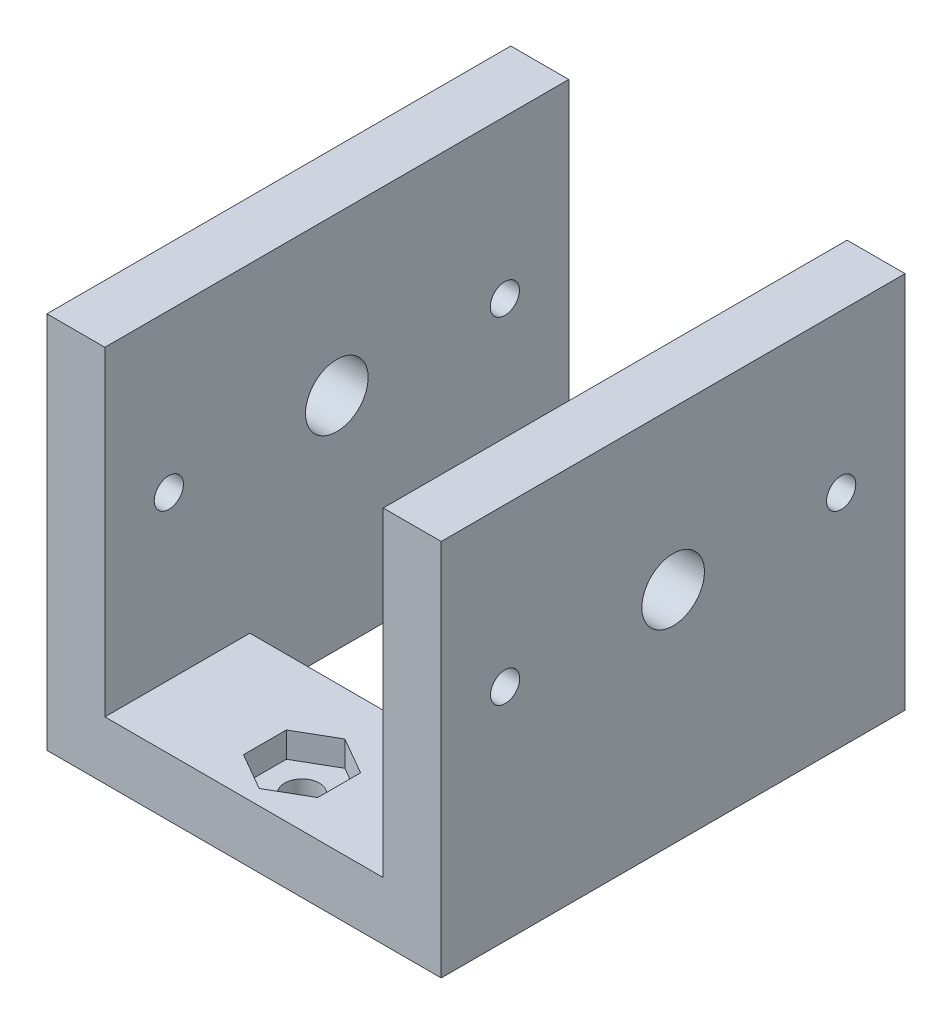
SolidWorks part; units mm, degrees
ref_plane "Front Plane" through (0, 0, 0) normal (0, 0, 1) x (1, 0, 0)
ref_plane "Top Plane" through (0, 0, 0) normal (0, 1, 0) x (1, 0, 0)
ref_plane "Right Plane" through (0, 0, 0) normal (1, 0, 0) x (0, 0, -1)
sketch "Sketch1" plane through (0, 0, 0) normal (0, 0, 1) x (1, 0, 0)
  line L0 (-26.9408, -26.9408) -> (0, 0) construction
  line L1 (0, 0) -> (26.9408, -26.9408) construction
  line L2 (-45.4545, 0) -> (50.5549, 0) construction
  line L7 (-26.9408, -17.4158) -> (-26.9408, 39.7342)
  line L9 (26.9408, 39.7342) -> (26.9408, -17.4158)
  line L11 (15, -48.5349) -> (-15, -48.5349) construction
  line L12 (-26.9408, -36.4658) -> (26.9408, -36.4658)
  line L13 (-26.9408, 39.7342) -> (26.9408, 39.7342)
  line L14 (-26.9408, 26.9408) -> (0, 0) construction
  line L15 (26.9408, 26.9408) -> (0, 0) construction
  circle A0 centre (0, 0) radius 38.1 construction
  circle A1 centre (-26.9408, -26.9408) radius 4.445
  circle A2 centre (26.9408, -26.9408) radius 4.445
  arc A3 (-26.9408, -17.4158) -> (-26.9408, -36.4658) centre (-26.9408, -26.9408) ccw
  arc A4 (26.9408, -36.4658) -> (26.9408, -17.4158) centre (26.9408, -26.9408) ccw
  circle A5 centre (0, 0) radius 50.8 construction
  circle A6 centre (-26.9408, 26.9408) radius 9.525 construction
  circle A7 centre (26.9408, 26.9408) radius 9.525 construction
  dimension "D1" = 76.2
  dimension "D4" = 8.89
  dimension "D5" = 8.89
  dimension "D6" = 19.05
  dimension "D7" = 19.05
  dimension "D8" = 57.15
  dimension "D9" = 101.6
  dimension "D11" = 19.05
  dimension "D13" = 19.05
  dimension "D2" = 45
  dimension "D3" = 45
  dimension "D10" = 30
  dimension "D12" = 45
  dimension "D14" = 45
extrude "Boss-Extrude1" add sketch "Sketch1" along normal blind 12.7 and the other way blind 12.7
sketch "Sketch9" plane through (0, 0, 12.7) normal (0, 0, 1) x (1, 0, 0)
  line L0 (-26.9408, 39.7342) -> (26.9408, 39.7342) construction
  line L1 (-15.24, 39.7342) -> (15.24, 39.7342)
  line L2 (-15.24, 39.7342) -> (-15.24, 4.6822)
  line L3 (-15.24, 4.6822) -> (15.24, 4.6822)
  line L4 (15.24, 39.7342) -> (15.24, 4.6822)
  line L5 (-15.24, 39.7342) -> (15.24, 4.6822) construction
  line L6 (-15.24, 4.6822) -> (15.24, 39.7342) construction
  point P0 (0, 22.2082)
  dimension "D1" = 30.48
  dimension "D2" = 35.052
extrude "Cut-Extrude6" cut sketch "Sketch9" against normal through all
sketch "Sketch10" plane through (0, 0, 12.7) normal (0, 0, 1) x (1, 0, 0)
  line L0 (-26.9408, 39.7342) -> (-26.9408, -1.6678)
  line L2 (-26.9408, -1.6678) -> (26.9408, -1.6678)
  line L3 (26.9408, 39.7342) -> (26.9408, -17.4158) construction
  line L5 (26.9408, -1.6678) -> (26.9408, 39.7342)
  line L6 (26.9408, 39.7342) -> (15.24, 39.7342)
  line L7 (15.24, 39.7342) -> (15.24, 4.6822)
  line L8 (15.24, 4.6822) -> (-15.24, 4.6822)
  line L9 (-15.24, 4.6822) -> (-15.24, 39.7342)
  line L10 (-15.24, 39.7342) -> (-26.9408, 39.7342)
  dimension "D1" = 6.35
extrude "Boss-Extrude3" add sketch "Sketch10" along normal blind 12.7
mirror "Mirror4" about plane through (0, 0, 0) normal (0, 0, 1) of "Boss-Extrude3"
sketch "Sketch11" plane through (0, 0, 25.4) normal (0, 0, 1) x (1, 0, 0)
  line L1 (-26.9408, 39.7342) -> (-21.59, 39.7342)
  line L2 (-26.9408, 39.7342) -> (-26.9408, -17.4158)
  line L3 (-26.9408, -17.4158) -> (-21.59, -17.4158)
  line L4 (-21.59, 39.7342) -> (-21.59, -17.4158)
  line L5 (-15.24, 4.6822) -> (-15.24, 39.7342) construction
  dimension "D1" = 6.35
extrude "Cut-Extrude7" cut sketch "Sketch11" against normal through all
mirror "Mirror5" about plane through (0, 0, 0) normal (1, 0, 0) of "Cut-Extrude7"
sketch "Sketch12" plane through (0, -36.4658, 0) normal (0, -1, 0) x (1, 0, 0)
  line L0 (15.24, -25.4) -> (15.24, 25.4) construction
  line L1 (-15.24, 9.525) -> (15.24, 9.525)
  line L2 (-15.24, 9.525) -> (-15.24, -9.525)
  line L3 (-15.24, -9.525) -> (15.24, -9.525)
  line L4 (15.24, 9.525) -> (15.24, -9.525)
  line L5 (-15.24, 9.525) -> (15.24, -9.525) construction
  line L6 (-15.24, -9.525) -> (15.24, 9.525) construction
  point P0 (0, 0)
  point P2 (15.24, 9.525)
  dimension "D1" = 19.05
extrude "Cut-Extrude8" cut sketch "Sketch12" against normal through all
sketch "Sketch14" plane through (-21.59, 0, 0) normal (-1, 0, 0) x (0, 0, 1)
  line L0 (-25.4, 4.6822) -> (-9.525, 4.6822) construction
  circle A0 centre (-18.4, 22.4622) radius 1.6
  dimension "D1" = 3.2
  dimension "D2" = 17.78
  dimension "D3" = 18.4
extrude "Cut-Extrude9" cut sketch "Sketch14" against normal through all
mirror "Mirror6" about plane through (0, 0, 0) normal (0, 0, 1) of "Cut-Extrude9"
sketch "Sketch15" plane through (21.59, 0, 0) normal (1, 0, 0) x (0, 0, -1)
  line L0 (0, -17.4158) -> (0, 39.7342) construction
  line L1 (-18.4, 22.4622) -> (18.4, 22.4622) construction
  line L2 (0, 38.1) -> (0, -38.1) construction
  circle A0 centre (0, 22.4622) radius 3.429
  dimension "D1" = 6.858
extrude "Cut-Extrude10" cut sketch "Sketch15" against normal through all
sketch "Sketch18" plane through (0, 4.6822, 0) normal (0, 1, 0) x (1, 0, 0)
  line L0 (-26.9408, 0) -> (26.9408, 0) construction
  line L1 (4.064, 21.3964) -> (0, 23.7427)
  line L2 (0, 23.7427) -> (-4.064, 21.3964)
  line L3 (-4.064, 21.3964) -> (-4.064, 16.7036)
  line L4 (-4.064, 16.7036) -> (0, 14.3573)
  line L5 (0, 14.3573) -> (4.064, 16.7036)
  line L6 (4.064, 16.7036) -> (4.064, 21.3964)
  circle A0 centre (0, 19.05) radius 4.064 construction
  point P1 (-10.414, 17.3524)
  point P9 (-10.414, 16.6574)
  point P10 (-10.414, 0)
  point P11 (-0.0041, 16.8504)
  point P12 (0, 21.3773)
  dimension "D1" = 8.128
  dimension "D2" = 19.05
extrude "Cut-Extrude11" cut sketch "Sketch18" against normal blind 2.7781
mirror "Mirror7" about plane through (0, 0, 0) normal (0, 0, 1) of "Cut-Extrude11"
hole_wizard "#6 Clearance Hole1" positions "Sketch20" profile "Sketch22" hole size "#6" standard "ANSI Inch" end condition through all
sketch "Sketch20" plane through (0, 1.9041, 0) normal (0, 1, 0) x (1, 0, 0)
  line L1 (0, 23.7427) -> (0, 14.3573) construction
  point P0 (0, 19.05)
  point P10 (-9.6167, 0)
  point P11 (0, 19.05)
sketch "Sketch22" plane through (0, 1.9041, -19.05) normal (1, 0, 0) x (0, 0, 1)
  line L0 (0, 0) -> (0, 38.3699)
  line L1 (0, 38.3699) -> (1.8986, 38.3699)
  line L2 (1.8986, 38.3699) -> (1.8986, 0)
  line L5 (1.8986, 0) -> (0, 0)
  line L11 (0, -6.35) -> (0, 107.95) construction
  dimension "Thru Hole Dia." = 3.7973
  dimension "Thru Hole Depth" = 38.3699
mirror "Mirror8" about plane through (0, 0, 0) normal (0, 0, 1) of "#6 Clearance Hole1"
sketch "Sketch24" plane through (0, 0, -25.4) normal (0, 0, -1) x (-1, 0, 0)
  line L1 (-21.59, -1.6678) -> (21.59, -1.6678)
  line L2 (-21.59, -1.6678) -> (-21.59, 39.7342)
  line L3 (-21.59, 39.7342) -> (21.59, 39.7342)
  line L4 (21.59, -1.6678) -> (21.59, 39.7342)
sketch "Sketch25" plane through (0, 0, -12.7) normal (0, 0, -1) x (-1, 0, 0)
  line L0 (-21.59, -1.6678) -> (21.59, -1.6678) construction
  line L1 (-44.148, -1.6678) -> (45.6656, -1.6678)
  line L2 (-44.148, -1.6678) -> (-44.148, -41.125)
  line L3 (-44.148, -41.125) -> (45.6656, -41.125)
  line L4 (45.6656, -1.6678) -> (45.6656, -41.125)
extrude "Cut-Extrude14" cut sketch "Sketch25" against normal through all
